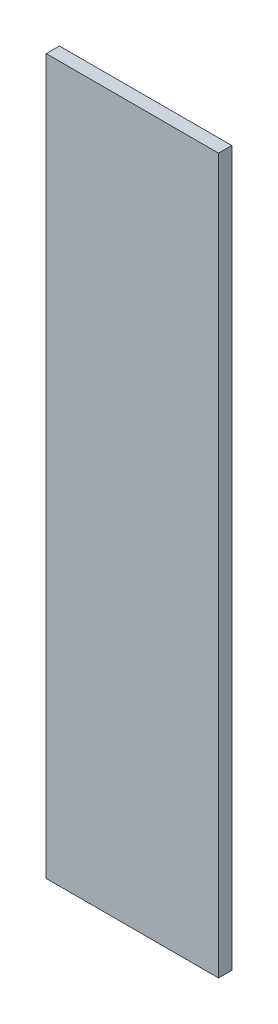
SolidWorks part; units mm, degrees
material "Balsa"
ref_plane "Plan de face" through (0, 0, 0) normal (0, 0, 1) x (1, 0, 0)
ref_plane "Plan de dessus" through (0, 0, 0) normal (0, 1, 0) x (1, 0, 0)
ref_plane "Plan de droite" through (0, 0, 0) normal (1, 0, 0) x (0, 0, -1)
sketch "Esquisse1" plane through (0, 0, 0) normal (0, 0, 1) x (1, 0, 0)
  line L1 (65.1211, 0) -> (0, 0)
  line L2 (65.1211, 0) -> (65.1211, 270)
  line L3 (65.1211, 270) -> (0, 270)
  line L4 (0, 0) -> (0, 270)
  dimension "D1" = 270
  dimension "D2" = 65.1211
extrude "Boss.-Extru.1" add sketch "Esquisse1" against normal blind 5
